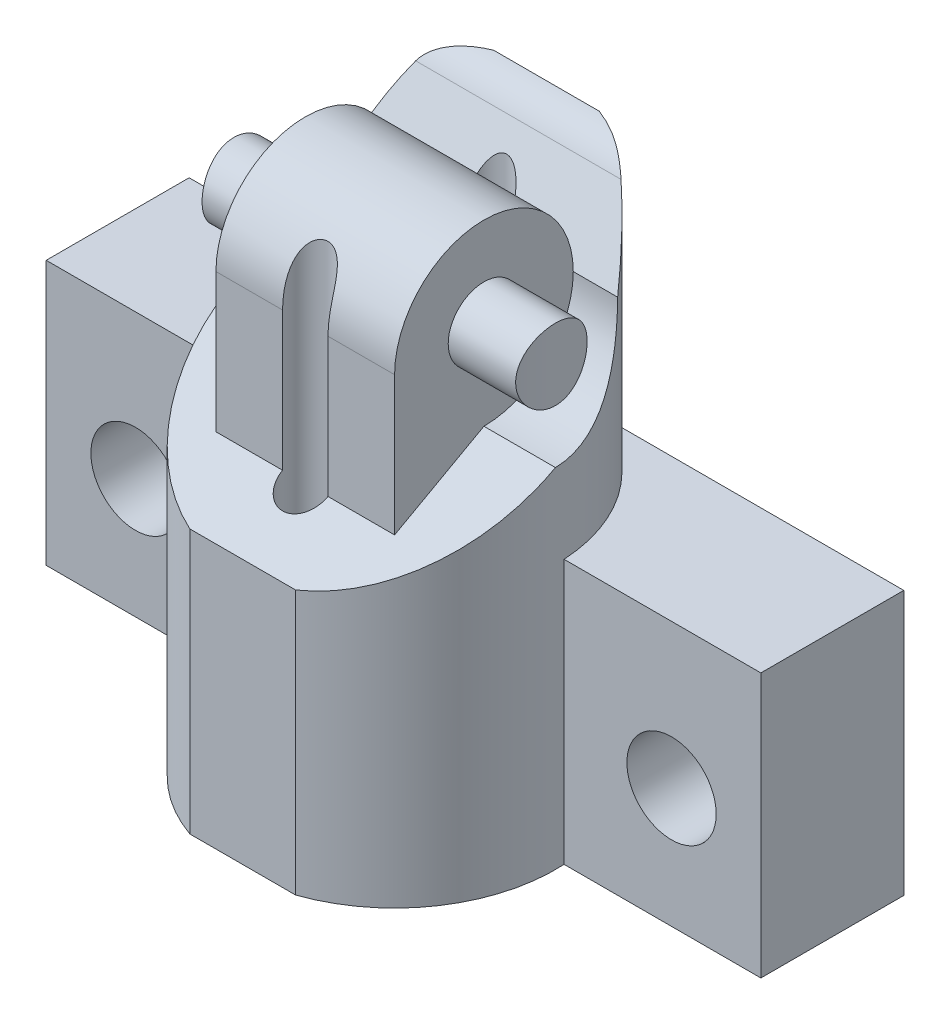
SolidWorks part; units mm, degrees
ref_plane "Front Plane" through (0, 0, 0) normal (0, 0, 1) x (1, 0, 0)
ref_plane "Top Plane" through (0, 0, 0) normal (0, 1, 0) x (1, 0, 0)
ref_plane "Right Plane" through (0, 0, 0) normal (1, 0, 0) x (0, 0, -1)
sketch "Sketch1" plane through (0, 0, 0) normal (0, 1, 0) x (1, 0, 0)
  line L0 (-2.958, 8.5) -> (2.958, 8.5)
  line L1 (-2.958, -8.5) -> (2.958, -8.5)
  arc A0 (-2.958, 8.5) -> (-2.958, -8.5) centre (0, 0) ccw
  arc A1 (2.958, 8.5) -> (2.958, -8.5) centre (0, 0) cw
  point P9 (-9, 0)
  point P10 (9, 0)
  dimension "D1" = 18
  dimension "D2" = 17
extrude "Boss-Extrude1" add sketch "Sketch1" along normal blind 45
sketch "Sketch2" plane through (0, 0, 0) normal (0, -1, 0) x (1, 0, 0)
  circle A0 centre (0, -5) radius 1.27
  circle A1 centre (0, 5) radius 1.27
  dimension "D1" = 2.54
  dimension "D2" = 5
  dimension "D3" = 5
extrude "Cut-Extrude1" cut sketch "Sketch2" against normal blind 51.256
sketch "Sketch3" plane through (0, 0, -8.5) normal (0, 0, -1) x (-1, 0, 0)
  line L0 (5, 0) -> (5, 10)
  line L1 (5, 10) -> (-5, 10)
  line L2 (-5, 10) -> (-5, 0)
  line L3 (5, 0) -> (-5, 0)
  line L4 (-2.958, 0) -> (2.958, 0) construction
  point P10 (0, 0)
  dimension "D1" = 10
  dimension "D2" = 10
extrude "Cut-Extrude2" cut sketch "Sketch3" against normal up to surface (17 mm away) up to face at (0, 22.5, 8.5)
sketch "Sketch4" plane through (5, 0, 0) normal (-1, 0, 0) x (0, 0, 1)
  line L0 (-7.4833, 10) -> (-5, 5)
  line L1 (8.5, 12.3086) -> (5, 5)
  line L2 (7.4833, 0) -> (-7.4833, 0) construction
  line L3 (-7.4833, 10) -> (-9.8579, -1.8222)
  line L4 (-9.8579, -1.8222) -> (9.8579, -1.8222)
  line L6 (8.5, 45) -> (8.5, 10) construction
  line L7 (9.8579, -1.8222) -> (8.5, 12.3086)
  arc A0 (-5, 5) -> (5, 5) centre (0, 5) ccw
  circle A1 centre (0, 5) radius 2.05
  point P7 (0, 0)
  dimension "D1" = 4.1
  dimension "D2" = 5
  dimension "D3" = 12.0584
  dimension "D4" = 37.769
extrude "Cut-Extrude3" cut sketch "Sketch4" against normal mid plane 35
ref_plane "Plane1" through (-2.958, 0, 0) normal (-1, 0, 0) x (0, 0, 1)
sketch "Sketch6" plane through (-2.958, 0, 0) normal (-1, 0, 0) x (0, 0, 1)
  line L0 (8.5, 30.2956) -> (0, 35)
  line L1 (8.5, 45) -> (8.5, 12.3086) construction
  line L3 (8.5, 45) -> (-8.5, 45) construction
  line L4 (8.5, 30.2956) -> (18.3464, 50.6263)
  line L7 (-8.5, 45) -> (18.3464, 50.6263)
  line L8 (8.5, 45) -> (8.5, 12.3086) construction
  line L12 (-5, 40) -> (-6.926, 43.8779)
  line L13 (-5, 5) -> (-7.4833, 10) construction
  arc A0 (0, 35) -> (-5, 40) centre (0, 40) cw
  circle A1 centre (0, 40) radius 2
  arc A3 (-6.926, 43.8779) -> (-8.5, 45) centre (-8.7637, 42.9652) ccw
  dimension "D1" = 5
  dimension "D3" = 4
  dimension "D2" = 5
  dimension "D4" = 8.5
extrude "Cut-Extrude5" cut sketch "Sketch6" against normal blind 9.6 from surface starting at face at (5, 7.05, 0)
sketch "Sketch7" plane through (5, 0, 0) normal (1, 0, 0) x (0, 0, -1)
  line L3 (-8.5, 45) -> (-8.5, 12.3086) construction
  line L4 (-5, 40) -> (-5, 32.2327)
  line L5 (-7.4833, 45) -> (7.4833, 45) construction
  line L6 (-5, 32.2327) -> (-8.5, 30.2956)
  line L8 (0, 35) -> (-7.4833, 30.8583) construction
  line L10 (8.5, 45) -> (18.9606, 55.6302)
  line L11 (18.9606, 55.6302) -> (-10.6436, 58.7694)
  line L12 (-10.6436, 58.7694) -> (-8.5, 30.2956)
  line L14 (8.5, 45) -> (8.5, 10) construction
  line L15 (5, 40) -> (6.926, 43.8779)
  arc A0 (5, 40) -> (-5, 40) centre (0, 40) ccw
  arc A4 (6.926, 43.8779) -> (8.5, 45) centre (8.7637, 42.9652) cw
  dimension "D1" = 5
fillet "Fillet3" radius 1 2 edges at (0, 10, -3.73) (0, 10, 6.27)
extrude "Cut-Extrude6" cut sketch "Sketch6<3>" along normal blind 6.604 from surface starting at face at (-5, 2.95, 0)
sketch "Sketch6<3>" plane through (-2.958, 0, 0) normal (-1, 0, 0) x (0, 0, 1) same geometry as "Sketch6"
extrude "Cut-Extrude7" cut sketch "Sketch7" against normal blind 14.986
sketch "Sketch8" plane through (0, 10, 0) normal (0, -1, 0) x (1, 0, 0)
  line L0 (0, -1.5) -> (0, 1.5)
  line L1 (-2.958, -8.5) -> (2.958, -8.5) construction
  line L2 (2.958, 8.5) -> (-2.958, 8.5) construction
  line L3 (0, -8.5) -> (17.548, -23.9281)
  line L4 (17.548, -23.9281) -> (17.548, 21.762)
  line L5 (17.548, 21.762) -> (0, 8.5)
  arc A0 (0, -1.5) -> (0, -8.5) centre (0, -5) cw
  arc A1 (0, 1.5) -> (0, 8.5) centre (0, 5) cw
  circle A2 centre (0, 5) radius 2.27 construction
  circle A3 centre (0, -5) radius 2.27 construction
sketch "Sketch9" plane through (0, 0, 8.5) normal (0, 0, 1) x (1, 0, 0)
  line L1 (-50.665, 15.5072) -> (25.1207, 15.5072)
  line L2 (-50.665, 15.5072) -> (-50.665, -39.6102)
  line L3 (-50.665, -39.6102) -> (25.1207, -39.6102)
  line L4 (25.1207, 15.5072) -> (25.1207, -39.6102)
  point P4 (25.1207, -5.855)
  point P5 (-50.665, -39.6102)
extrude "Cut-Extrude9" cut sketch "Sketch9" against normal blind 51.308
fillet "Fillet4" radius 1 2 edges at (0, 15.5072, -3.73) (0, 15.5072, 6.27)
sketch "Sketch11" plane through (0, 0, 8.5) normal (0, 0, 1) x (1, 0, 0)
  line L0 (2.958, 15.5072) -> (-2.958, 15.5072) construction
  line L1 (-20, 15.5072) -> (20, 15.5072)
  line L2 (-20, 15.5072) -> (-20, 30.2956)
  line L3 (-20, 30.2956) -> (20, 30.2956)
  line L4 (20, 15.5072) -> (20, 30.2956)
  line L5 (-2.958, 30.2956) -> (2.958, 30.2956) construction
  circle A0 centre (15, 22.2017) radius 2.5
  circle A1 centre (-15, 22.2017) radius 2.5
  point P10 (0, 15.5072)
  point P11 (0, 0)
  dimension "D2" = 5
  dimension "D3" = 30
  dimension "D1" = 40
  dimension "D4" = 5
extrude "Boss-Extrude2" add sketch "Sketch11" against normal up to surface (17 mm away) from offset 9 up to face at (0, 30.2536, -8.5) offset against normal yes
